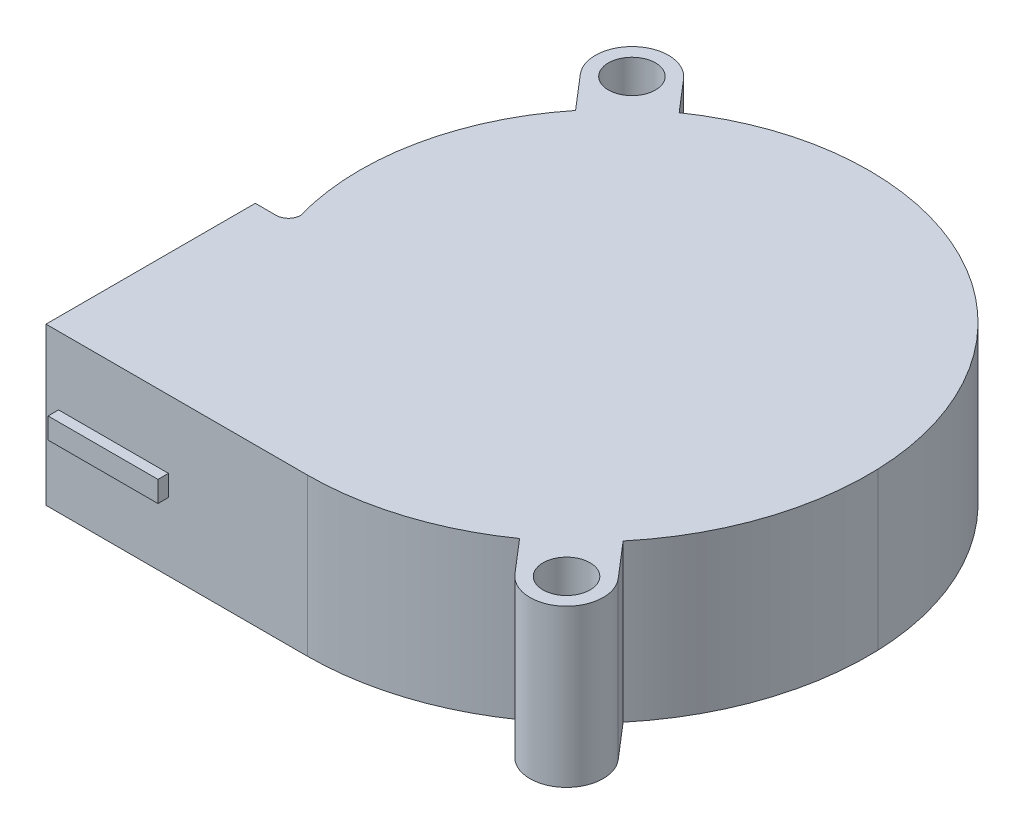
SolidWorks part; units mm, degrees
ref_plane "Front Plane" through (0, 0, 0) normal (0, 0, 1) x (1, 0, 0)
ref_plane "Top Plane" through (0, 0, 0) normal (0, 1, 0) x (1, 0, 0)
ref_plane "Right Plane" through (0, 0, 0) normal (1, 0, 0) x (0, 0, -1)
sketch "Sketch1" plane through (0, 0, 0) normal (0, 1, 0) x (1, 0, 0)
  line L0 (-12.25, 0) -> (-22.75, 0) construction
  line L1 (12.25, 0) -> (26.75, 0) construction
  line L2 (0, -12.25) -> (0, -15.834) construction
  line L3 (0, 12.25) -> (0, 24.25) construction
  line L4 (-2.1574, -24) -> (4.1608, -24) construction
  line L5 (0, -27.75) -> (-25, -27.75)
  line L6 (-23, -7.75) -> (-23, -27.75) construction
  line L7 (0, 24.25) -> (0, 0) construction
  line L8 (-25, -27.75) -> (-25, -7.75)
  line L9 (-23, -7.75) -> (-25, -7.75)
  line L10 (0, 24.25) -> (-17.5, 24.25) construction
  line L11 (-21, 20.75) -> (-21, 12.25) construction
  line L12 (17.25, -23.75) -> (17.25, -32.8048) construction
  line L13 (26.75, 0) -> (26.75, -39.4866) construction
  line L14 (20.75, -27.25) -> (46.3772, -27.25) construction
  line L15 (24.25, -23.75) -> (24.25, -17.4002) construction
  line L16 (-20.1542, 18.4685) -> (-17.378, 15.2386)
  line L17 (-14.8458, 23.0315) -> (-12.2443, 20.0049)
  line L18 (15.3721, -22.8628) -> (18.0958, -26.0315)
  line L19 (20.5256, -18.1195) -> (23.4042, -21.4685)
  circle A0 centre (0, 0) radius 12.25 construction
  arc A1 (-22.75, 0) -> (-17.378, 15.2386) centre (1.5495, 0) cw
  arc A2 (0, 24.25) -> (26.75, 0) centre (1.6043, -0.8591) cw
  arc A3 (26.75, 0) -> (20.5256, -18.1195) centre (-0.0682, -0.9163) cw
  arc A4 (-22.75, 0) -> (-21.8314, -6.5814) centre (1.2843, 0) ccw
  arc A5 (-23, -7.75) -> (-21.8314, -6.5814) centre (-23, -6.5814) ccw
  arc A6 (-14.8458, 23.0315) -> (-20.1542, 18.4685) centre (-17.5, 20.75) ccw
  arc A7 (18.0958, -26.0315) -> (23.4042, -21.4685) centre (20.75, -23.75) ccw
  arc A8 (-12.2443, 20.0049) -> (0, 24.25) centre (1.5495, 0) cw
  arc A9 (15.3721, -22.8628) -> (0, -27.75) centre (-0.0682, -0.9163) cw
  circle A10 centre (-17.5, 20.75) radius 2.25
  circle A11 centre (20.75, -23.75) radius 2.25
  dimension "D1" = 24.5
  dimension "D12" = 24.0343
  dimension "D13" = 1.1686
  dimension "D15" = 7
  dimension "D17" = 7
  dimension "D20" = 4.5
  dimension "D21" = 4.5
  dimension "D2" = 10.5
  dimension "D3" = 14.5
  dimension "D4" = 15.5
  dimension "D5" = 52
  dimension "D6" = 20
  dimension "D7" = 2
  dimension "D8" = 24
  dimension "D9" = 25
  dimension "D10" = 55.5
  dimension "D11" = 20
  dimension "D14" = 2
  dimension "D16" = 4
  dimension "D18" = 0.5
  dimension "D19" = 2.5
extrude "Boss-Extrude1" add sketch "Sketch1" along normal blind 7.5 and the other way blind 7.5
sketch "Sketch2" plane through (0, 0, 0) normal (0, 1, 0) x (1, 0, 0)
  line L0 (-22.75, 0) -> (-23.75, 0) construction
  line L1 (-23.3754, 4.25) -> (-22.3754, 4.25)
  line L2 (-23.3713, -4.25) -> (-22.3713, -4.25)
  line L3 (-22.3754, 4.25) -> (-20.4761, 3.2423)
  line L4 (-20.4761, 3.2423) -> (-20.1069, -2.9638)
  line L5 (-20.1069, -2.9638) -> (-22.3713, -4.25)
  arc A0 (-22.75, 0) -> (-21.8314, -6.5814) centre (1.2843, 0) ccw construction
  arc A1 (-17.378, 15.2386) -> (-22.75, 0) centre (1.5495, 0) ccw construction
  spline S0 degree 2 poles (-23.3713, -4.25) (-24.1266, -0.0004) (-23.3754, 4.25) knots 0 0 0 1 1 1
  dimension "D1" = 1
  dimension "D2" = 4.25
  dimension "D3" = 4.25
  dimension "D4" = 1
  dimension "D5" = 1
extrude "Boss-Extrude2" add sketch "Sketch2" along normal blind 1 and the other way blind 2
sketch "Sketch3" plane through (0, 0, 0) normal (0, 1, 0) x (1, 0, 0)
  line L0 (-25, -27.75) -> (0, -27.75) construction
  line L1 (-23.8, -27.75) -> (-13.3, -27.75)
  line L2 (-23.8, -27.75) -> (-23.8, -28.75)
  line L3 (-23.8, -28.75) -> (-13.3, -28.75)
  line L4 (-13.3, -27.75) -> (-13.3, -28.75)
  line L5 (-25, -7.75) -> (-25, -27.75) construction
  dimension "D1" = 1.2
  dimension "D2" = 1
  dimension "D3" = 10.5
extrude "Boss-Extrude3" add sketch "Sketch3" along normal blind 1 and the other way blind 1
